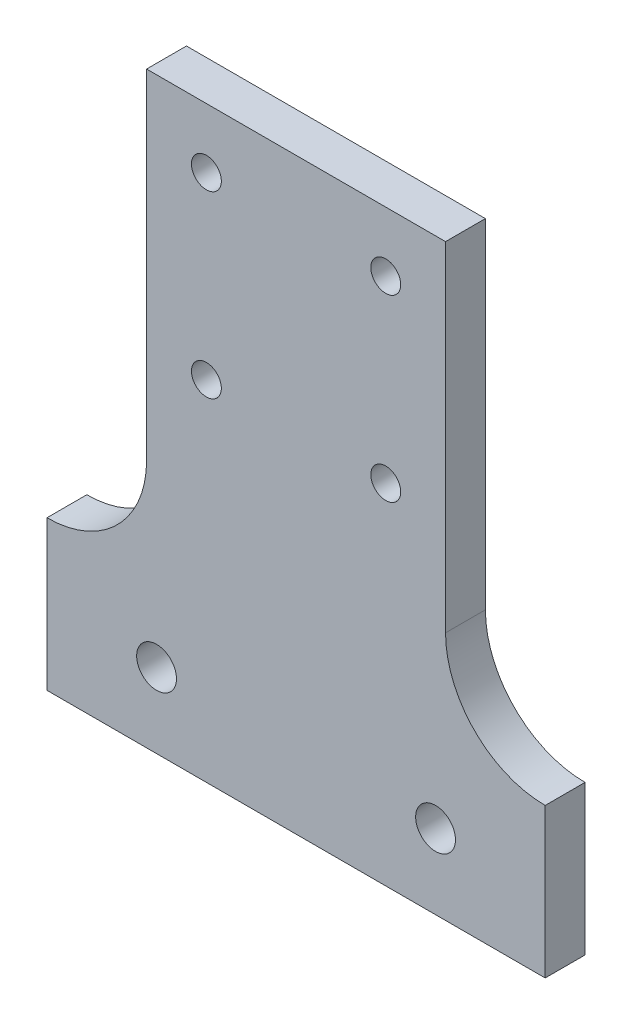
SolidWorks part; units mm, degrees
material "A-玻璃纤维"
ref_plane "前视基准面" through (0, 0, 0) normal (0, 0, 1) x (1, 0, 0)
ref_plane "上视基准面" through (0, 0, 0) normal (0, 1, 0) x (1, 0, 0)
ref_plane "右视基准面" through (0, 0, 0) normal (1, 0, 0) x (0, 0, -1)
sketch "草图1" plane through (0, 0, 0) normal (0, 0, 1) x (1, 0, 0)
  line L0 (0, 0) -> (0, 55.8998) construction
  line L5 (25, 0) -> (-25, 0)
  line L6 (-25, 0) -> (-25, 15)
  line L7 (25, 0) -> (25, 15)
  line L8 (-25, 15) -> (-15, 15)
  line L9 (25, 15) -> (15, 15)
  line L10 (-15, 15) -> (-15, 59)
  line L11 (15, 15) -> (15, 59)
  line L12 (-15, 59) -> (15, 59)
  point P13 (0, 59)
  dimension "D1" = 15
  dimension "D2" = 50
  dimension "D3" = 30
  dimension "D4" = 44
extrude "凸台-拉伸1" add sketch "草图1" along normal blind 4
sketch "草图2" plane through (0, 0, 4) normal (0, 0, 1) x (1, 0, 0)
  line L0 (0, 59) -> (0, 44) construction
  line L1 (15, 59) -> (-15, 59) construction
  line L3 (-9, 53) -> (9, 53) construction
  line L4 (-9, 53) -> (-9, 35) construction
  line L5 (-9, 35) -> (9, 35) construction
  line L6 (9, 53) -> (9, 35) construction
  line L7 (-9, 53) -> (9, 35) construction
  line L8 (-9, 35) -> (9, 53) construction
  circle A0 centre (-9, 53) radius 1.5
  circle A1 centre (-9, 35) radius 1.5
  circle A2 centre (9, 35) radius 1.5
  circle A3 centre (9, 53) radius 1.5
  dimension "D4" = 3
  dimension "D1" = 15
  dimension "D2" = 18
  dimension "D3" = 18
extrude "切除-拉伸1" cut sketch "草图2" against normal through all
sketch "草图3" plane through (0, 0, 4) normal (0, 0, 1) x (1, 0, 0)
  line L0 (0, 59) -> (0, 0) construction
  line L1 (15, 59) -> (-15, 59) construction
  line L2 (-25, 0) -> (25, 0) construction
  circle A0 centre (-14, 7.5) radius 2
  circle A1 centre (14, 7.5) radius 2
  dimension "D1" = 7.5
  dimension "D3" = 4
  dimension "D2" = 14
extrude "切除-拉伸2" cut sketch "草图3" against normal through all
fillet "圆角1" radius 10 2 edges at (-15, 15, 2) (15, 15, 2)
